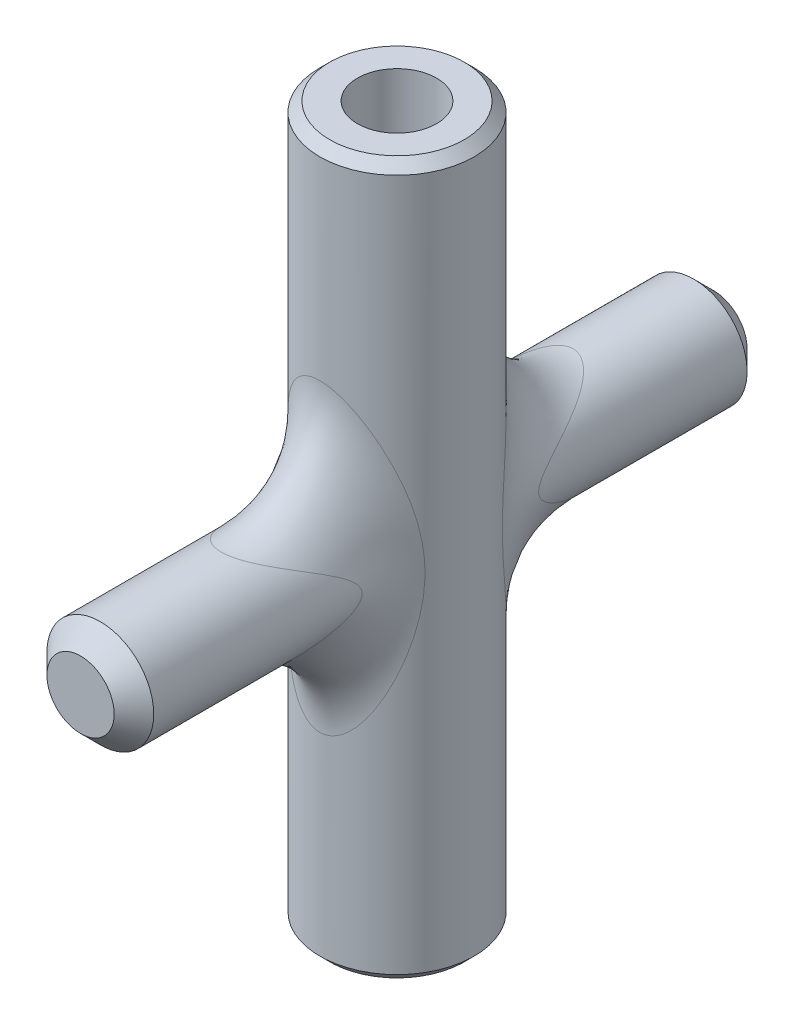
SolidWorks part; units mm, degrees
ref_plane "Front Plane" through (0, 0, 0) normal (0, 0, 1) x (1, 0, 0)
ref_plane "Top Plane" through (0, 0, 0) normal (0, 1, 0) x (1, 0, 0)
ref_plane "Right Plane" through (0, 0, 0) normal (1, 0, 0) x (0, 0, -1)
ref_axis "Axis1" through (3.135, 0, 0) along (-1, 0, 0)
sketch "Sketch1" plane through (0, 0, 0) normal (0, 0, 1) x (1, 0, 0)
  circle A0 centre (0, 0) radius 2.7
  dimension "D1" = 5.4
extrude "Boss-Extrude1" add sketch "Sketch1" along normal blind 16
chamfer "Chamfer1" distance 1 angle 45 1 edges at (2.7, 0, 16)
pattern_circular "CirPattern1" count 2 over 360 about axis through (3.135, 0, 0) along (-1, 0, 0) of "Boss-Extrude1", "Chamfer1"
sketch "Sketch2" plane through (0, 0, 0) normal (0, 1, 0) x (1, 0, 0)
  circle A0 centre (0, 0) radius 3.9
  dimension "D1" = 7.8
extrude "Boss-Extrude2" add sketch "Sketch2" along normal blind 18
chamfer "Chamfer2" distance 0.5 angle 45 1 edges at (0, 18, 3.9)
pattern_circular "CirPattern2" count 2 over 360 about axis through (3.135, 0, 0) along (-1, 0, 0) of "Boss-Extrude2", "Chamfer2"
sketch "Sketch3" plane through (0, 18, 0) normal (0, 1, 0) x (1, 0, 0)
  circle A0 centre (0, 0) radius 2
  dimension "D1" = 4
extrude "Cut-Extrude1" cut sketch "Sketch3" against normal up to next
fillet "Fillet1" radius 5 2 edges at (-2.7, 0, -2.8142) (2.7, 0, 2.8142)
